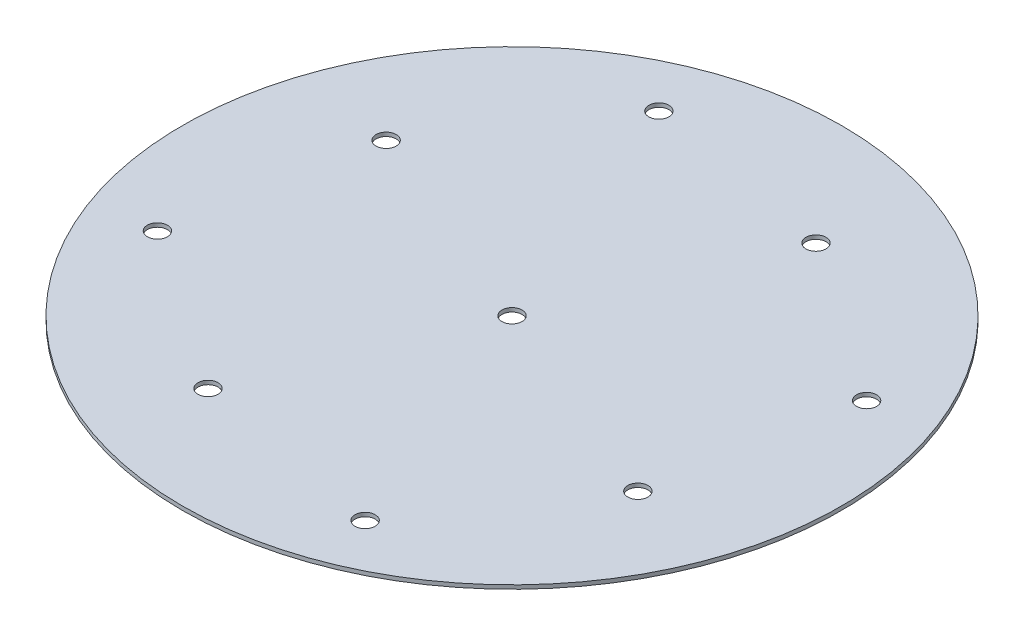
SolidWorks part; units mm, degrees
ref_plane "Front Plane" through (0, 0, 0) normal (0, 0, 1) x (1, 0, 0)
ref_plane "Top Plane" through (0, 0, 0) normal (0, 1, 0) x (1, 0, 0)
ref_plane "Right Plane" through (0, 0, 0) normal (1, 0, 0) x (0, 0, -1)
sketch "Sketch2" plane through (0, 0, 0) normal (1, 0, 0) x (0, 0, -1)
  line L0 (0, 0) -> (-84.9998, 0)
  line L1 (-84.9998, 0) -> (-84.9998, 1)
  line L2 (-84.9998, 1) -> (0, 1)
  line L5 (0, 1) -> (0, 0)
  dimension "D1" = 84.9998
  dimension "D2" = 1
ref_axis "Axis1" through (0, -0.75, 0) along (0, 1, 0)
revolve "Revolve1" add sketch "Sketch2" angle 360 about axis through (0, -0.75, 0) along (0, 1, 0)
hole_wizard "#6 (0.204) Diameter Hole1" positions "Sketch6" profile "Sketch7" hole size "#6" standard "ANSI Inch" end condition through all
sketch "Sketch6" plane through (0, 1, 0) normal (0, 1, 0) x (1, 0, 0)
  line L0 (0, 0) -> (-53.438, 129.0108) construction
  line L2 (0, 0) -> (0, 109.0908) construction
  line L3 (0, 0) -> (-78.5296, 32.528) construction
  circle A0 centre (0, 0) radius 84.9998 construction
  point P0 (-26.7878, 64.6716)
  point P11 (264.7437, 73.7878)
  point P20 (-55.4328, 22.961)
  dimension "D1" = 22.5
  dimension "D2" = 70
  dimension "D3" = 60
  dimension "D4" = 45
sketch "Sketch7" plane through (-26.7878, 1, -64.6716) normal (1, 0, 0) x (0, 0, 1)
  line L0 (0, 0) -> (0, 1)
  line L1 (0, 1) -> (2.5908, 1)
  line L2 (2.5908, 1) -> (2.5908, 0)
  line L5 (2.5908, 0) -> (0, 0)
  line L11 (0, -6.35) -> (0, 107.95) construction
  dimension "Thru Hole Dia." = 5.1816
  dimension "Thru Hole Depth" = 1
pattern_circular "CirPattern3" count 4 over 360 about axis through (0, -0.75, 0) along (0, 1, 0) of "#6 (0.204) Diameter Hole1"
hole_wizard "#6 (0.204) Diameter Hole2" positions "Sketch8" profile "Sketch9" hole size "#6" standard "ANSI Inch" end condition through all
sketch "Sketch8" plane through (0, 1, 0) normal (0, 1, 0) x (1, 0, 0)
  line L0 (0, 0) -> (106.3094, -1.7118) construction
  point P7 (0, 0)
sketch "Sketch9" plane through (0, 1, 0) normal (1, 0, 0) x (0, 0, 1)
  line L0 (0, 0) -> (0, 1)
  line L1 (0, 1) -> (2.5908, 1)
  line L2 (2.5908, 1) -> (2.5908, 0)
  line L5 (2.5908, 0) -> (0, 0)
  line L11 (0, -6.35) -> (0, 107.95) construction
  dimension "Thru Hole Dia." = 5.1816
  dimension "Thru Hole Depth" = 1
